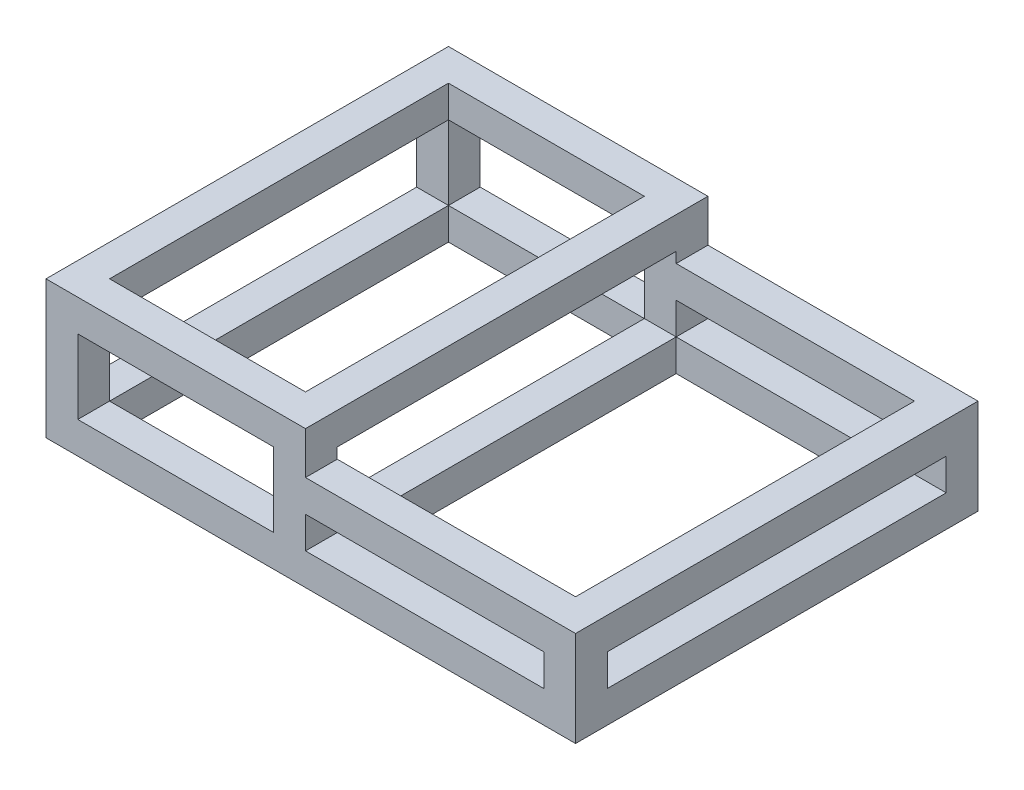
SolidWorks part; units mm, degrees
ref_plane "Front Plane" through (0, 0, 0) normal (0, 0, 1) x (1, 0, 0)
ref_plane "Top Plane" through (0, 0, 0) normal (0, 1, 0) x (1, 0, 0)
ref_plane "Right Plane" through (0, 0, 0) normal (1, 0, 0) x (0, 0, -1)
sketch "Sketch1" plane through (0, 0, 0) normal (0, 0, 1) x (1, 0, 0)
  line L0 (250, 25) -> (-5, 25)
  line L5 (250, -65) -> (-250, -65)
  line L6 (250, -65) -> (250, 65)
  line L7 (250, 65) -> (-250, 65)
  line L8 (-250, -65) -> (-250, 65)
  line L9 (250, -65) -> (-250, 65) construction
  line L10 (250, 65) -> (-250, -65) construction
  line L11 (-5, 25) -> (-5, 65)
  line L12 (-35, -10) -> (-60, -10)
  line L13 (-250, 35) -> (-5, 35)
  line L14 (-250, 35) -> (-250, 65)
  line L15 (-250, 65) -> (-5, 65)
  line L16 (-5, 35) -> (-5, 65)
  line L17 (-250, -65) -> (250, -65)
  line L18 (-250, -65) -> (-250, -35)
  line L19 (-250, -35) -> (250, -35)
  line L20 (250, -65) -> (250, -35)
  line L21 (250, 25) -> (-5, 25)
  line L22 (250, 25) -> (250, -5)
  line L23 (250, -5) -> (-5, -5)
  line L24 (-5, 25) -> (-5, -5)
  line L25 (-35, 35) -> (-5, 35)
  line L26 (-35, 35) -> (-35, -35)
  line L27 (-35, -35) -> (-5, -35)
  line L28 (-5, 35) -> (-5, -35)
  line L29 (-250, 35) -> (-220, 35)
  line L30 (-250, 35) -> (-250, -35)
  line L31 (-250, -35) -> (-220, -35)
  line L32 (-220, 35) -> (-220, -35)
  line L33 (250, -35) -> (220, -35)
  line L34 (250, -35) -> (250, -5)
  line L35 (250, -5) -> (220, -5)
  line L36 (220, -35) -> (220, -5)
  line L37 (-60, -35) -> (-60, -10)
  line L38 (-47.5, -22.5) -> (-47.5, -10) construction
  line L39 (-60, -22.5) -> (-47.5, -22.5) construction
  circle A0 centre (-47.5, -22.5) radius 10
  point P0 (0, 0)
  dimension "D11" = 20
  dimension "D1" = 500
  dimension "D2" = 130
  dimension "D4" = 255
  dimension "D3" = 30
  dimension "D5" = 30
  dimension "D6" = 30
  dimension "D7" = 30
  dimension "D8" = 30
  dimension "D9" = 30
  dimension "D10" = 90
  dimension "D12" = 25
extrude "Boss-Extrude1" add sketch "Sketch1" along normal blind 380 contours L0 L11 L7 L8 L5 L6 | L22 L21 L24 L23 | L34 L33 L36 L35 | L18 L17 L20 L19 | L30 L29 L32 L31 | L14 L13 L16 L15 | L25 L26 L27 L28 region at (0, -50, 0)
sketch "Sketch2" plane through (0, 65, 0) normal (0, 1, 0) x (1, 0, 0)
  line L0 (-5, 0) -> (-250, 0) construction
  line L1 (-250, 0) -> (-250, -380) construction
  line L2 (-250, -380) -> (-5, -380) construction
  line L3 (-5, -380) -> (-5, 0) construction
  line L4 (250, 0) -> (-5, 0) construction
  line L5 (-5, 0) -> (-5, -380) construction
  line L6 (-5, -380) -> (250, -380) construction
  line L7 (250, -380) -> (250, 0) construction
  line L8 (250, 0) -> (-5, 0)
  line L9 (-5, 0) -> (-5, -380)
  line L10 (-5, -380) -> (250, -380)
  line L11 (250, -380) -> (250, 0)
  line L12 (-5, 0) -> (-250, 0)
  line L13 (-250, 0) -> (-250, -380)
  line L14 (-250, -380) -> (-5, -380)
  line L15 (-5, -380) -> (-5, 0)
  line L16 (-220, -30) -> (-220, -350)
  line L21 (-220, -350) -> (-35, -350)
  line L22 (-35, -30) -> (-35, -350)
  line L23 (-35, -30) -> (-220, -30)
  line L28 (-5, -30) -> (220, -30)
  line L29 (220, -30) -> (220, -350)
  line L30 (220, -350) -> (-5, -350)
  line L31 (-35, -164.9359) -> (-51.5426, -170.7949)
  line L34 (25, -190) -> (289.3766, -190) construction
  line L40 (-35, -215.0641) -> (-51.5426, -209.2051)
  circle A0 centre (-50, -190) radius 10
  arc A1 (-51.5426, -170.7949) -> (-51.5426, -209.2051) centre (-44.7406, -190) ccw
  point P19 (-35, -190)
  line M18 (-5, -380) -> (-5, 0)
  dimension "D3" = 30
  dimension "D4" = 20
  dimension "D2" = 30
  dimension "D5" = 15
  dimension "D1" = 30
extrude "Cut-Extrude1" cut sketch "Sketch2" against normal through all contours L34 L16 L21 L22 L40 A1 | L16 L34 A1 L31 L22 L23 | L34 L29 L28 M18 | L34 L15 L30 L29 | L34 A1 L40 L22 A0 | A1 L34 A0 L22 L31 | A0 L34 | L34 A0 region at (107.5, 65, 33.9118) region at (-129.0268, 65, 190) region at (-35.5848, 65, 190) region at (-50, 65, 190)
sketch "Sketch3" plane through (250, 0, 0) normal (1, 0, 0) x (0, 0, -1)
  line L8 (-30, -35) -> (-30, -5)
  line L9 (-30, -5) -> (-350, -5)
  line L10 (-350, -5) -> (-350, -35)
  line L11 (-350, -35) -> (-30, -35)
  line L12 (-30, -35) -> (-30, -5)
  line L13 (-30, -5) -> (-350, -5)
  line L14 (-350, -5) -> (-350, -35)
  line L15 (-350, -35) -> (-30, -35)
  dimension "D1" = 30
extrude "Cut-Extrude2" cut sketch "Sketch3" against normal up to surface (30 mm away) up to face at (220, -20, 190)
sketch "Sketch4" plane through (-250, 0, 0) normal (-1, 0, 0) x (0, 0, 1)
  line L8 (350, 35) -> (30, 35)
  line L9 (30, 35) -> (30, -35)
  line L10 (30, -35) -> (350, -35)
  line L11 (350, -35) -> (350, 35)
  line L12 (350, 35) -> (30, 35)
  line L13 (30, 35) -> (30, -35)
  line L14 (30, -35) -> (350, -35)
  line L15 (350, -35) -> (350, 35)
  dimension "D1" = 30
extrude "Cut-Extrude3" cut sketch "Sketch4" against normal up to surface (245 mm away) contours L14 L15 L12 L13 region at (-250, 0, 190) up to face at (-5, -3.75, 190)
equation "\"Rover_Length\"= 25in"
equation "\"Rover_Width\"= 18in"
equation "\"Rover_Height\"= 12in"
equation "\"Chassis_Wheelbase\"= 28in"
equation "\"Chassis_WheelDiam\"= 171mm"
equation "\"Chassis_ArmDiamWidth\"= 0.75in"
equation "\"Chassis_ArmAngle\"= 135deg"
equation "\"Chassis_ArmHeight\"= 8in"
equation "\"Chassis_HubMountOD\"= 3in"
equation "\"Chassis_WheelBoltHole\"= 36mm"
equation "\"Chassis_WheelBoltNum\"= 4"
equation "\"Chassis_DiffBarLength\"= 12in"
equation "\"Chassis_DiffBarWidth\"= 1in"
equation "\"Chassis_DiffBarHeight\"= 0.5in"
equation "\"Chassis_DiffLinkage_Length\"= 2.5in"
equation "\"Chassis_MountBracketThickness\"= 0.125in"
equation "\"Chassis_MountBracketWidth\"= 3in"
equation "\"Chassis_MountBacketOverlap\"= 0.5in"
equation "\"Chassis_ArmShaftDiam\"= 0.75in"
equation "\"Chassis_ArmHoleSpacing\" = 1.25in"
equation "\"Chassis_Length\" = 500mm"
equation "\"Chassis_Width\" = 380mm"
equation "\"Chassis_Thickness\" = 130mm"
equation "\"D1@Boss-Extrude1\"=\"Chassis_Width\""
equation "\"D2@Sketch1\"=\"Chassis_Thickness\""
equation "\"Chassis_Mod_Mount_Length\" = 255mm"
equation "\"D4@Sketch1\"=\"Chassis_Mod_Mount_Length\""
equation "\"Chassis_Extrusion_Profile\" = 30mm"
equation "\"D3@Sketch1\"=\"Chassis_Extrusion_Profile\""
equation "\"D5@Sketch1\"=\"Chassis_Extrusion_Profile\""
equation "\"D6@Sketch1\"=\"Chassis_Extrusion_Profile\""
equation "\"D7@Sketch1\"=\"Chassis_Extrusion_Profile\""
equation "\"D8@Sketch1\"=\"Chassis_Extrusion_Profile\""
equation "\"D9@Sketch1\"=\"Chassis_Extrusion_Profile\""
equation "\"D1@Sketch2\"=\"Chassis_Extrusion_Profile\""
equation "\"D2@Sketch2\"=\"Chassis_Extrusion_Profile\""
equation "\"D1@Sketch3\"=\"Chassis_Extrusion_Profile\""
equation "\"D1@Sketch4\"=\"Chassis_Extrusion_Profile\""
equation "\"D3@Sketch2\"=\"Chassis_Extrusion_Profile\""
equation "\"D1@Sketch1\"=\"Chassis_Length\""
equation "\"D10@Sketch1\"=\"Chassis_Extrusion_Profile\"*3"
